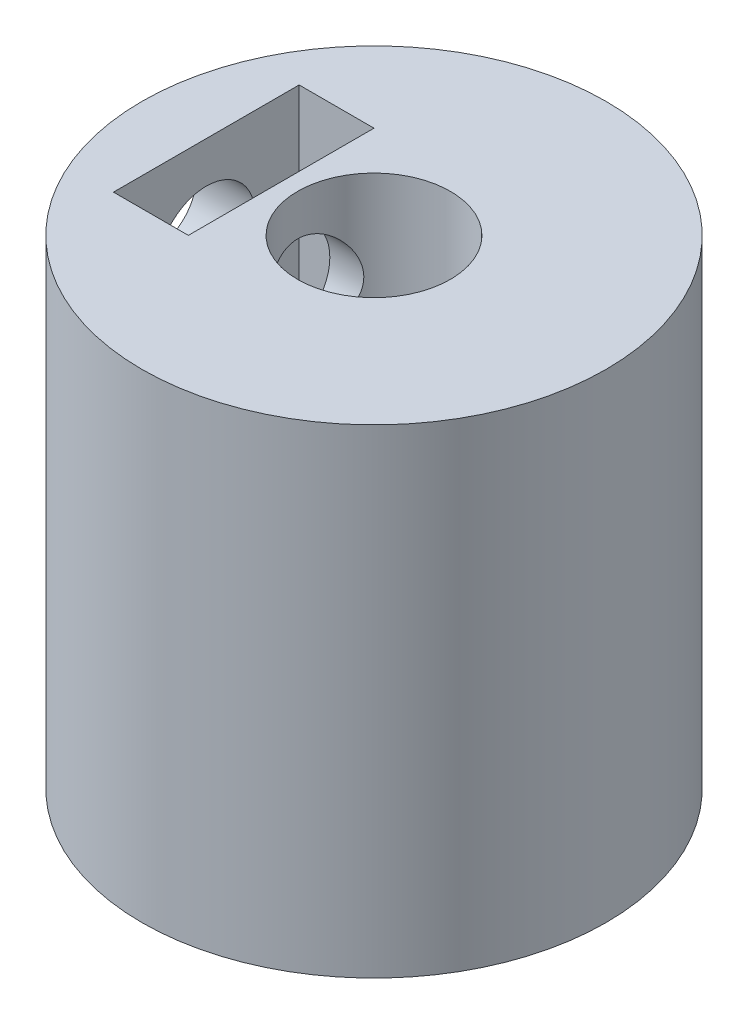
SolidWorks part; units mm, degrees
ref_plane "Front Plane" through (0, 0, 0) normal (0, 0, 1) x (1, 0, 0)
ref_plane "Top Plane" through (0, 0, 0) normal (0, 1, 0) x (1, 0, 0)
ref_plane "Right Plane" through (0, 0, 0) normal (1, 0, 0) x (0, 0, -1)
sketch "Sketch1" plane through (0, 0, 0) normal (0, 1, 0) x (1, 0, 0)
  circle A0 centre (0, 0) radius 2.55
  circle A1 centre (0, 0) radius 7.75
  point P4 (-4.3, 0)
  dimension "D1" = 5.1
  dimension "D2" = 15.5
extrude "Boss-Extrude2" add sketch "Sketch1" along normal blind 8 and the other way blind 8 contours A1 A0 region at (-7.5308, 0, 0)
sketch "Sketch2" plane through (0, 0, 0) normal (1, 0, 0) x (0, 0, -1)
  line L2 (7.75, 8) -> (-7.75, 8) construction
  line L3 (-7.75, -8) -> (7.75, -8) construction
  circle A0 centre (0, 5) radius 1.625
  circle A1 centre (0, -5) radius 1.625
  dimension "D3" = 3.25
  dimension "D4" = 3.25
  dimension "D2" = 3
  dimension "D1" = 3
extrude "Cut-Extrude1" cut sketch "Sketch2" against normal blind 20.5
sketch "Sketch4" plane through (0, 0, 0) normal (1, 0, 0) x (0, 0, -1)
  line L0 (7.75, 8) -> (-7.75, 8) construction
  line L1 (3.1, 1.9) -> (-3.1, 1.9)
  line L2 (3.1, 1.9) -> (3.1, 8)
  line L3 (3.1, 8) -> (-3.1, 8)
  line L4 (-3.1, 1.9) -> (-3.1, 8)
  line L5 (3.1, 1.9) -> (-3.1, 8) construction
  line L6 (3.1, 8) -> (-3.1, 1.9) construction
  line L7 (0, 0) -> (13.4724, 0) construction
  line L8 (3.1, -8) -> (-3.1, -1.9) construction
  line L9 (3.1, -1.9) -> (-3.1, -8) construction
  line L10 (-3.1, -1.9) -> (-3.1, -8)
  line L11 (3.1, -8) -> (-3.1, -8)
  line L12 (3.1, -1.9) -> (3.1, -8)
  line L13 (3.1, -1.9) -> (-3.1, -1.9)
  circle A0 centre (0, 5) radius 1.625 construction
  point P0 (0, 4.95)
  point P16 (0, -4.95)
  dimension "D2" = 3.1
  dimension "D1" = 6.2
extrude "Cut-Extrude2" cut sketch "Sketch4" against normal blind 2.5 from offset 3.1 offset against normal yes
